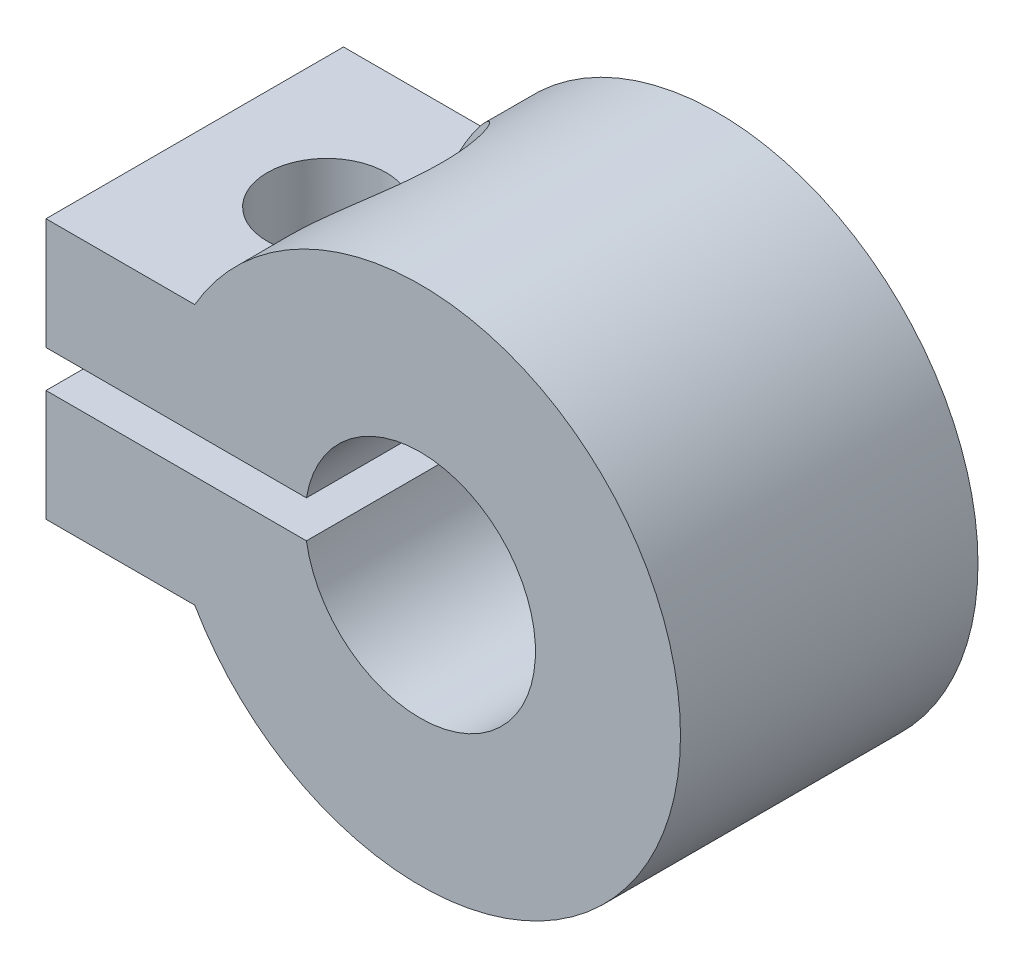
SolidWorks part; units mm, degrees
ref_plane "Front Plane" through (0, 0, 0) normal (0, 0, 1) x (1, 0, 0)
ref_plane "Top Plane" through (0, 0, 0) normal (0, 1, 0) x (1, 0, 0)
ref_plane "Right Plane" through (0, 0, 0) normal (1, 0, 0) x (0, 0, -1)
sketch "Sketch1" plane through (0, 0, 0) normal (0, 0, 1) x (1, 0, 0)
  line L0 (-6.0622, 3.5) -> (-10.0622, 3.5)
  line L1 (-10.0622, 3.5) -> (-10.0622, 0.5)
  line L2 (-10.0622, 0.5) -> (-3.0594, 0.5)
  line L3 (-3.0594, -0.5) -> (-10.0622, -0.5)
  line L4 (-10.0622, -0.5) -> (-10.0622, -3.5)
  line L5 (-10.0622, -3.5) -> (-6.0622, -3.5)
  line L6 (-10.0622, -0.5) -> (-10.0622, 0.5) construction
  arc A0 (-3.0594, -0.5) -> (-3.0594, 0.5) centre (0, 0) ccw
  arc A1 (-6.0622, -3.5) -> (-6.0622, 3.5) centre (0, 0) ccw
  point P13 (-10.0622, 0)
  dimension "D2" = 7
  dimension "D3" = 3.1
  dimension "D1" = 3
  dimension "D4" = 0.5
  dimension "D5" = 4
extrude "Boss-Extrude1" add sketch "Sketch1" along normal blind 8
sketch "Sketch2" plane through (0, 3.5, 0) normal (0, 1, 0) x (1, 0, 0)
  line L0 (-10.0622, -8) -> (-10.0622, 0) construction
  circle A0 centre (-6.5622, -3.9514) radius 1.6
  circle A1 centre (-6.5622, -3.9514) radius 3.1 construction
  point P2 (-10.0622, -4)
  dimension "D1" = 6.2
  dimension "D2" = 3.2
  dimension "D3" = 3.5
extrude "Cut-Extrude1" cut sketch "Sketch2" against normal through all
sketch "Sketch3" plane through (0, 3.5, 0) normal (0, 1, 0) x (1, 0, 0)
  circle A0 centre (-6.5622, -3.9514) radius 3.1
  dimension "D1" = 6.2
extrude "Cut-Extrude2" cut sketch "Sketch3" along normal through all
sketch "Sketch4" plane through (0, -3.5, 0) normal (0, -1, 0) x (1, 0, 0)
  circle A0 centre (-6.5622, 3.9514) radius 3.1
  dimension "D1" = 6.2
extrude "Cut-Extrude3" cut sketch "Sketch4" along normal through all contours A0
